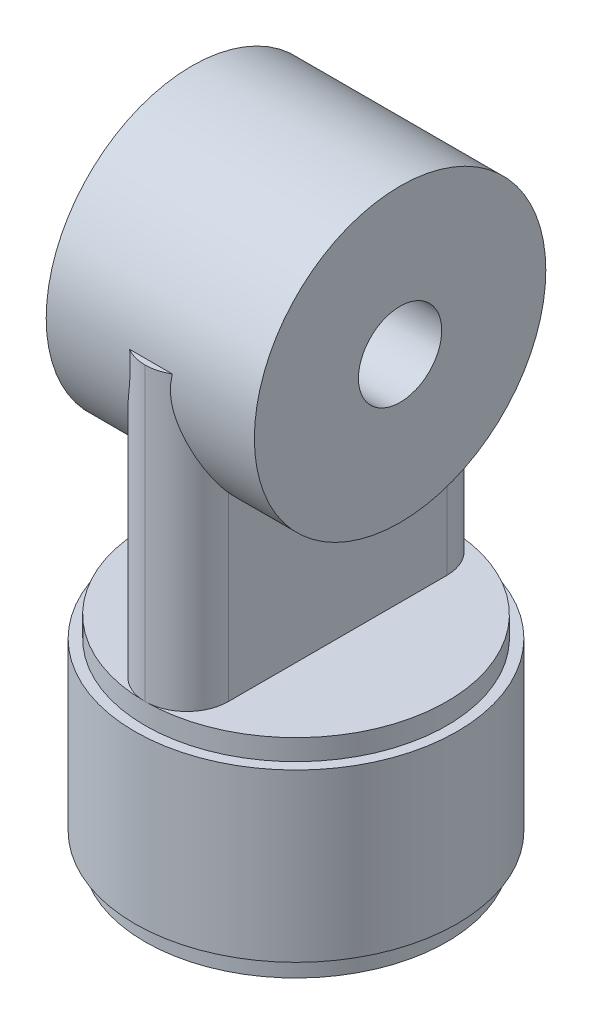
SolidWorks part; units mm, degrees
ref_plane "Plan de face" through (0, 0, 0) normal (0, 0, 1) x (1, 0, 0)
ref_plane "Plan de dessus" through (0, 0, 0) normal (0, 1, 0) x (1, 0, 0)
ref_plane "Plan de droite" through (0, 0, 0) normal (1, 0, 0) x (0, 0, -1)
sketch "Esquisse1" plane through (0, 0, 0) normal (0, 0, 1) x (1, 0, 0)
  line L0 (0, 190.2222) -> (0, -351.4074) construction
  line L1 (-5, 34.2423) -> (-36.2424, 34.2423)
  line L2 (-36.2424, 34.2423) -> (-36.2424, 39.2423)
  line L3 (-36.2424, 84.2423) -> (-32, 84.2423)
  line L4 (-32, 81.7138) -> (-32, 51.2423)
  line L5 (-30, 49.2423) -> (-25, 49.2423)
  line L6 (-25, 49.2423) -> (-25, 46.2338)
  line L7 (-25, 46.2338) -> (-5, 46.2338)
  line L9 (-5, 46.2338) -> (-5, 34.2423)
  line L10 (-32, 84.2423) -> (0, 84.2423)
  line L11 (0, 84.2423) -> (0, 81.7138)
  line L12 (0, 81.7138) -> (-32, 81.7138)
  line L13 (-38.7054, 79.2423) -> (-38.7054, 39.2423)
  line L14 (-36.2424, 79.2423) -> (-36.2424, 84.2423)
  line L15 (-36.2424, 79.2423) -> (-38.7054, 79.2423)
  line L16 (-36.2424, 39.2423) -> (-38.7054, 39.2423)
  arc A0 (-32, 51.2423) -> (-30, 49.2423) centre (-30, 51.2423) ccw
  point P13 (-32, 49.2423)
  point P16 (-32, 84.2423)
  dimension "D2" = 2
  dimension "D3" = 40
  dimension "D8" = 5
  dimension "D1" = 35
  dimension "D4" = 5
  dimension "D5" = 20
  dimension "D6" = 5
  dimension "D7" = 50
  dimension "D9" = 5
revolve "Révolution1" add sketch "Esquisse1" angle 360 about L0
sketch "Esquisse2" plane through (0, 84.2423, 0) normal (0, 1, 0) x (1, 0, 0)
  line L0 (0, 27.4421) -> (0, -49.1784) construction
  line L3 (-10, 34.8355) -> (-10, -34.8355)
  line L4 (10, 34.8355) -> (10, -34.8355)
  circle A3 centre (0, 0) radius 36.2424 construction
  arc A4 (10, 34.8355) -> (-10, 34.8355) centre (0, 0) ccw
  arc A5 (10, -34.8355) -> (-10, -34.8355) centre (0, 0) cw
  dimension "D1" = 10
extrude "Boss.-Extru.1" add sketch "Esquisse2" along normal blind 70
ref_plane "Plan1" through (0, 0, 0) normal (-1, 0, 0) x (0, 0, 1)
sketch "Esquisse6" plane through (0, 0, 0) normal (-1, 0, 0) x (0, 0, 1)
  line L0 (-34.8355, 154.2423) -> (34.8355, 154.2423) construction
  line L1 (-34.8355, 154.2423) -> (-34.8355, 84.2423) construction
  line L2 (34.8355, 154.2423) -> (34.8355, 84.2423) construction
  arc A2 (-34.8355, 154.2423) -> (34.8355, 154.2423) centre (0, 150.8525) cw
  arc A3 (-34.8355, 154.2423) -> (34.8355, 154.2423) centre (0, 150.8525) ccw
  dimension "D1" = 35
extrude "Boss.-Extru.2" add sketch "Esquisse6" along normal mid plane 50
sketch "Esquisse7" plane through (-25, 0, 0) normal (-1, 0, 0) x (0, 0, 1)
  line L0 (-35, 150.8525) -> (35, 150.8525) construction
  circle A0 centre (0, 150.8525) radius 35 construction
  circle A1 centre (0, 150.8525) radius 10
  dimension "D1" = 20
extrude "Enlèv. mat.-Extru.1" cut sketch "Esquisse7" against normal blind 50
fillet "Congé3" radius 10 4 edges at (10, 115.8525, -34.8355) (-10, 115.8525, -34.8355) (10, 115.8525, 34.8355) (-10, 115.8525, 34.8355)
scale "Echelle1" scale about centroid uniform scaling yes scale factor 0.25
